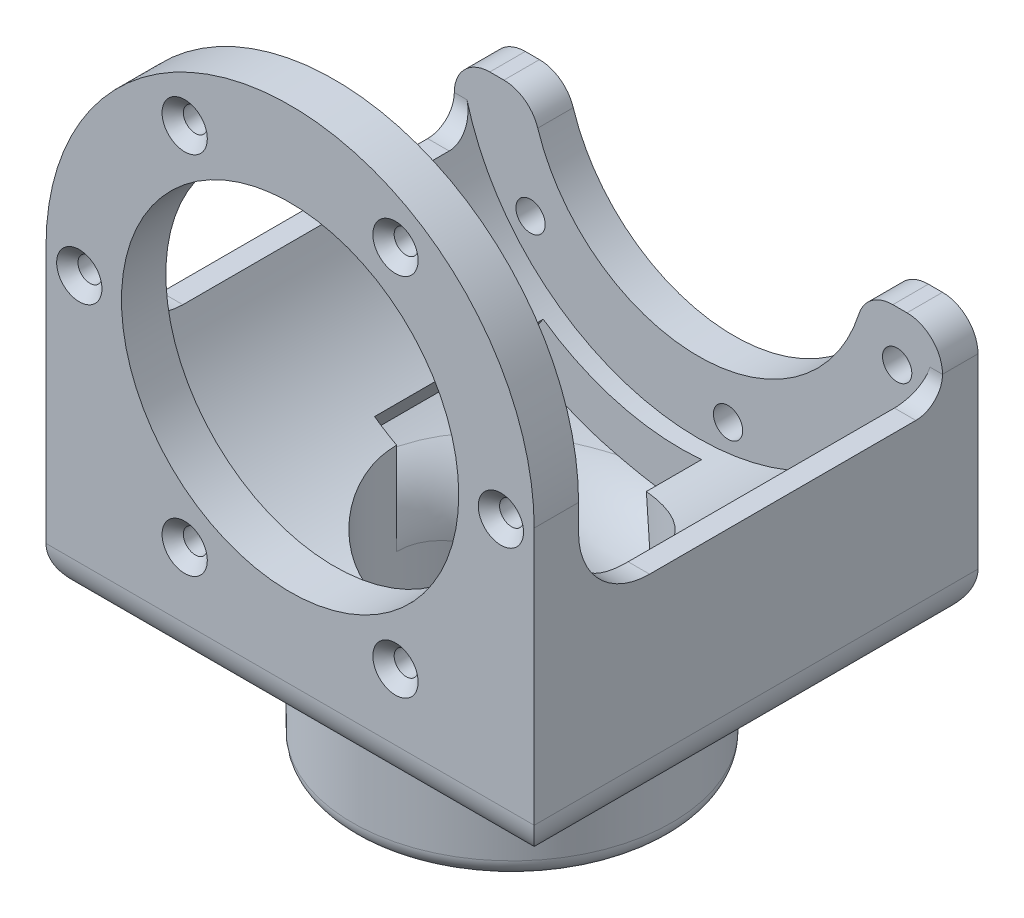
SolidWorks part; units mm, degrees
material "PLA"
ref_plane "Front Plane" through (0, 0, 0) normal (0, 0, 1) x (1, 0, 0)
ref_plane "Top Plane" through (0, 0, 0) normal (0, 1, 0) x (1, 0, 0)
ref_plane "Right Plane" through (0, 0, 0) normal (1, 0, 0) x (0, 0, -1)
sketch "Sketch1" plane through (0, 0, 0) normal (0, 1, 0) x (1, 0, 0)
  line L0 (0, 20.5) -> (0, -20.5) construction
  line L1 (-27.5, 20.5) -> (27.5, 20.5)
  line L2 (-27.5, 20.5) -> (-27.5, -20.5)
  line L3 (-27.5, -20.5) -> (27.5, -20.5)
  line L4 (27.5, 20.5) -> (27.5, -20.5)
  line L7 (27.5, 0) -> (0, 0) construction
  line L8 (0, 0) -> (-27.5, 0) construction
  dimension "D1" = 55
  dimension "D2" = 41
extrude "Boss-Extrude1" add sketch "Sketch1" along normal blind 23
sketch "Sketch3" plane through (0, 0, 20.5) normal (0, 0, 1) x (1, 0, 0)
  line L0 (27.5, 23) -> (27.5, 0) construction
  line L1 (-27.5, 0) -> (27.5, 0)
  line L2 (-27.5, 0) -> (-27.5, 33)
  line L3 (-27.5, 33) -> (27.5, 33) construction
  line L4 (27.5, 0) -> (27.5, 33)
  arc A0 (-27.5, 33) -> (27.5, 33) centre (0, 33) cw
  circle A1 centre (0, 33) radius 19
  circle A2 centre (0, 33) radius 18.5 construction
  dimension "D2" = 38
  dimension "D3" = 37
  dimension "D1" = 33
extrude "Boss-Extrude2" add sketch "Sketch3" along normal blind 5
sketch "Sketch5" plane through (0, 0, 25.5) normal (0, 0, 1) x (1, 0, 0)
  line L0 (-19, 33) -> (0, 33) construction
  line L1 (0, 33) -> (19, 33) construction
  line L2 (0, 33) -> (0, 14) construction
  line L3 (0, 33) -> (0, 52) construction
  line L4 (-19, 33) -> (-27.5, 33) construction
  line L5 (19, 33) -> (27.5, 33) construction
  line L6 (27.5, 34) -> (27.5, 33)
  line L7 (-27.5, 34) -> (-27.5, 33)
  circle A0 centre (0, 33) radius 19 construction
  arc A1 (-27.5, 33) -> (27.5, 33) centre (0, 33) cw
  arc A2 (27.5, 33) -> (-27.5, 33) centre (0, 33) ccw construction
  arc A3 (-27.5, 34) -> (27.5, 34) centre (0, 34) cw
  point P5 (0, 34)
  dimension "D2" = 27.5
  dimension "D1" = 1
extrude "Boss-Extrude3" add sketch "Sketch5" against normal up to surface (5 mm away) up to face at (0, 35.75, 20.5)
sketch "Sketch6" plane through (0, 0, 0) normal (0, -1, 0) x (1, 0, 0)
  line L0 (-27.5, 20.5) -> (27.5, 20.5) construction
  line L1 (-27.5, -20.5) -> (-27.5, 25.5) construction
  line L2 (27.5, 25.5) -> (27.5, -20.5) construction
  line L3 (-27.5, -19.5) -> (27.5, -19.5) construction
  line L5 (0, 20.5) -> (0, -19.5) construction
  line L6 (27.5, -20.5) -> (-27.5, -20.5) construction
  circle A0 centre (0, 0.5) radius 18
  dimension "D3" = 36
  dimension "D1" = 1
  dimension "D2" = 40
extrude "Boss-Extrude4" add sketch "Sketch6" along normal blind 14
sketch "Sketch4" plane through (0, 0, -20.5) normal (0, 0, -1) x (-1, 0, 0)
  line L0 (0, 0) -> (0, 6) construction
  line L1 (-19, 33) -> (0, 33) construction
  line L2 (0, 33) -> (19, 33) construction
  line L3 (0, 6) -> (0, 60) construction
  arc A1 (16.1555, 23) -> (-16.1555, 23) centre (0, 33) ccw construction
  circle A2 centre (0, 33) radius 26.5 construction
  circle A3 centre (0, 33) radius 18.5 construction
  circle A4 centre (0, 33) radius 27
  dimension "D1" = 53
  dimension "D2" = 37
  dimension "D3" = 54
extrude "Cut-Extrude1" cut sketch "Sketch4" against normal up to surface (41 mm away) up to face at (0, 36.0833, 20.5)
sketch "Sketch7" plane through (0, -14, 0) normal (0, -1, 0) x (1, 0, 0)
  circle A0 centre (0, 0.5) radius 13
  dimension "D1" = 26
extrude "Cut-Extrude2" cut sketch "Sketch7" against normal through all
sketch "Sketch8" plane through (0, 0, 25.5) normal (0, 0, 1) x (1, 0, 0)
  line L0 (0, 6) -> (0, 0) construction
  line L1 (-27.5, 0) -> (27.5, 0) construction
  line L2 (-5.45, 5.1) -> (5.45, 5.1)
  line L3 (-5.45, 5.1) -> (-5.45, 0.9)
  line L4 (-5.45, 0.9) -> (5.45, 0.9)
  line L5 (5.45, 5.1) -> (5.45, 0.9)
  circle A0 centre (0, 33) radius 27 construction
  point P10 (0, 0.9)
  dimension "D1" = 54
  dimension "D2" = 4.2
  dimension "D3" = 10.9
  dimension "D4" = 0.9
extrude "Cut-Extrude3" [suppressed] cut sketch "Sketch8" against normal up to surface (13.1976 mm away)
sketch "Sketch17" plane through (0, 0, -20.5) normal (0, 0, -1) x (-1, 0, 0)
  line L1 (-27.5, 23) -> (27.5, 23)
  line L2 (-27.5, 23) -> (-27.5, 0)
  line L3 (-27.5, 0) -> (27.5, 0)
  line L4 (27.5, 23) -> (27.5, 0)
extrude "Cut-Extrude5" cut sketch "Sketch17" against normal blind 1
ref_plane "Plane1" through (12.4779, 0, -12.4779) normal (0.7071, 0, -0.7071) x (0, 1, 0)
ref_axis "Axis1" through (0, 33, 25.5) along (0, 0, -1)
sketch "Sketch9" plane through (0, 0, 0) normal (1, 0, 0) x (0, 0, -1)
  line L0 (-0.5, -14) -> (-0.5, 23) construction
  line L1 (-18.5, -14) -> (17.5, -14) construction
  line L2 (-20.5, 23) -> (19.5, 23) construction
  line L3 (-25.5, 0) -> (19.5, 0) construction
  line L4 (-0.5, 8) -> (18.5, 8)
  line L5 (-0.5, 8) -> (-0.5, 1)
  line L6 (-0.5, 1) -> (18.5, 1)
  line L7 (18.5, 8) -> (18.5, 1)
  dimension "D1" = 19
  dimension "D2" = 7
  dimension "D3" = 1
revolve "Cut-Revolve1" cut sketch "Sketch9" angle 35 about axis through (0, 33, 25.5) along (0, 0, -1) other way angle 5
hole_wizard "CSK for M2.5 Flat Head Machine Screw2" positions "Sketch14" profile "Sketch13" countersink size "M2.5" standard "ANSI Metric" end condition through all
sketch "Sketch14" plane through (0, 0, 25.5) normal (0, 0, 1) x (1, 0, 0)
  line L0 (0, 33) -> (-23.75, 33) construction
  point P2 (-23.75, 33)
  dimension "D1" = 23.75
sketch "Sketch13" plane through (-23.75, 33, 25.5) normal (1, 0, 0) x (0, -1, 0)
  line L0 (0, 0) -> (0, 45)
  line L1 (0, 45) -> (1.35, 45)
  line L2 (1.35, 45) -> (1.35, 1.2)
  line L3 (1.35, 1.2) -> (2.55, 0)
  line L5 (2.55, 0) -> (0, 0)
  line L6 (-1.35, 1.2) -> (-2.55, 0) construction
  line L11 (0, -6.35) -> (0, 107.95) construction
  dimension "Thru Hole Dia." = 2.7
  dimension "Thru Hole Depth" = 45
  dimension "Near C'Sink Dia." = 5.1
  dimension "Near C'Sink Angle" = 90
pattern_circular "CirPattern1" count 6 over 360 about axis through (0, 33, 25.5) along (0, 0, -1) of "CSK for M2.5 Flat Head Machine Screw2"
sketch "Sketch16" plane through (12.4779, 0, -12.4779) normal (0.7071, 0, -0.7071) x (0, 1, 0)
  line L0 (-14, 18.3536) -> (-14, -17.6464) construction
  line L4 (-14, 0.3536) -> (0, 0.3536) construction
  line L5 (0, 5.6569) -> (0, -33.234) construction
  line L6 (0, 18.3536) -> (0, -17.6464) construction
  circle A1 centre (-5.2, 0.3536) radius 1.4
  dimension "D1" = 2.8
  dimension "D2" = 5.2
extrude "Cut-Extrude4" cut sketch "Sketch16" against normal blind 4
pattern_circular "CirPattern2" count 4 over 360 about axis through (0, 61.5, 0.5) along (0, -1, 0) of "Cut-Extrude4" reverse direction yes
sketch "Sketch19" plane through (0, 0, -19.5) normal (0, 0, -1) x (-1, 0, 0)
  line L0 (0, 33) -> (0, 9) construction
  line L1 (0, 33) -> (-3.3816, 9.2394) construction
  line L2 (-27.5, 0) -> (27.5, 0)
  line L3 (27.5, 0) -> (27.5, 30)
  line L4 (0, 33) -> (-22.2681, 24.0483) construction
  line L5 (27.5, 30) -> (18.7617, 30)
  line L6 (0, 33) -> (18.8864, 18.1911) construction
  line L7 (-27.5, 30) -> (-27.5, 0)
  line L8 (-18.7617, 30) -> (-27.5, 30)
  circle A0 centre (0, 33) radius 24 construction
  circle A1 centre (-3.3816, 9.2394) radius 1.55 construction
  circle A2 centre (-22.2681, 24.0483) radius 1.55 construction
  circle A5 centre (18.8864, 18.1911) radius 1.55 construction
  arc A6 (-18.7617, 30) -> (18.7617, 30) centre (0, 33) ccw
  circle A7 centre (0, 33) radius 19 construction
  point P12 (0, 33)
  point P13 (0, 33)
  dimension "D1" = 48
  dimension "D2" = 8.1
  dimension "D3" = 3.1
  dimension "D6" = 30
extrude "Boss-Extrude5" add sketch "Sketch19" along normal blind 5
sketch "Sketch25" plane through (0, 0, -24.5) normal (0, 0, -1) x (-1, 0, 0)
  line L0 (0, 14) -> (0, 33) construction
  line L1 (-3.3402, 9.2336) -> (0, 33) construction
  line L2 (0, 33) -> (-22.3909, 24.3601) construction
  line L3 (0, 33) -> (18.9123, 18.2241) construction
  circle A0 centre (0, 33) radius 24 construction
  arc A4 (-18.7617, 30) -> (18.7617, 30) centre (0, 33) ccw construction
  circle A5 centre (-3.3402, 9.2336) radius 1.4447 construction
  circle A6 centre (18.9123, 18.2241) radius 1.094 construction
  circle A7 centre (-22.3909, 24.3601) radius 1.7903 construction
  dimension "D1" = 48
  dimension "D4" = 60.9
  dimension "D2" = 8
  dimension "D3" = 60
sketch "Sketch22" plane through (0, 30, 0) normal (0, 1, 0) x (1, 0, 0)
  line L0 (27.5, 24.5) -> (27.5, 19.5) construction
  line L1 (-27.5, 19.5) -> (27.5, 19.5)
  line L2 (-27.5, 19.5) -> (-27.5, 20.5)
  line L3 (-27.5, 20.5) -> (27.5, 20.5)
  line L4 (27.5, 19.5) -> (27.5, 20.5)
  dimension "D1" = 1
extrude "Cut-Extrude6" cut sketch "Sketch22" against normal up to surface (7 mm away) up to face at (-5.472, 8.1822, -6.1909)
extrude "Cut-Extrude7" cut sketch "Sketch22<2>" against normal up to surface (7 mm away) up to face at (26.2899, 23, 0.5)
sketch "Sketch22<2>" plane through (0, 30, 0) normal (0, 1, 0) x (1, 0, 0) same geometry as "Sketch22"
hole_wizard "CSK for M3 Flat Head Machine Screw1" positions "Sketch20" profile "Sketch21" countersink size "M3" standard "ANSI Metric"
sketch "Sketch20" plane through (0, 0, -24.5) normal (0, 0, -1) x (-1, 0, 0)
  point P60 (-22.3909, 24.3601)
  point P63 (-3.3402, 9.2336)
  point P71 (18.9123, 18.2241)
sketch "Sketch21" plane through (22.3909, 24.3601, -24.5) normal (1, 0, 0) x (0, 1, 0)
  line L0 (0, 0) -> (0, 12)
  line L1 (0, 12) -> (1.65, 12)
  line L2 (1.65, 12) -> (1.65, 1.5)
  line L3 (1.65, 1.5) -> (3.15, 0)
  line L5 (3.15, 0) -> (0, 0)
  line L6 (-1.65, 1.5) -> (-3.15, 0) construction
  line L10 (0, 12) -> (-1.65, 12) construction
  line L11 (0, -6.35) -> (0, 107.95) construction
  dimension "Hole Dia." = 3.3
  dimension "Hole Depth" = 12
  dimension "Near C'Sink Dia." = 6.3
  dimension "Near C'Sink Angle" = 90
  dimension "Drill Angle" = 180
fillet "Fillet1" radius 2 1 edges at (0, -14, -17.5)
fillet "Fillet2" radius 8 1 edges at (-8.6521, 2.1919, -9.2026)
fillet "Fillet3" radius 5 4 edges at (27.5, 0, 0.5) (0, 0, 25.5) (-27.5, 0, 0.5) (0, 0, -24.5)
fillet "Fillet6" radius 8 2 edges at (-26.2899, 23, 20.5) (26.2899, 23, 20.5)
fillet "Fillet7" radius 4 4 edges at (-27.5, 30, -22.5) (-18.7617, 30, -22.5) (18.7617, 30, -22.5) (27.5, 30, -22.5)
fillet "Fillet8" radius 3 2 edges at (-26.2899, 23, -20.5) (26.2899, 23, -20.5)
sketch "Sketch27" plane through (0, 0, 25.5) normal (0, 0, 1) x (1, 0, 0)
  line L1 (-33.265, 65.2394) -> (37.3857, 65.2394)
  line L2 (-33.265, 65.2394) -> (-33.265, -15.0296)
  line L3 (-33.265, -15.0296) -> (37.3857, -15.0296)
  line L4 (37.3857, 65.2394) -> (37.3857, -15.0296)
extrude "Cut-Extrude8" [suppressed] cut sketch "Sketch27" against normal up to vertex
sketch "Sketch28" plane through (0, 23, 0) normal (0, 1, 0) x (1, 0, 0)
  line L0 (-18.0987, 20.5) -> (18.0987, 20.5) construction
  line L1 (-0.9257, 20.5) -> (46.0253, 20.5)
  line L2 (-41.1901, 20.5) -> (-41.1901, -57.2501)
  line L3 (-41.1901, -57.2501) -> (46.0253, -57.2501)
  line L4 (46.0253, 20.5) -> (46.0253, -57.2501)
  line L7 (-41.1901, 20.5) -> (-41.1901, 37.8555)
  line L8 (-41.1901, 37.8555) -> (-0.9257, 37.8555)
  line L9 (-0.9257, 20.5) -> (-0.9257, 37.8555)
extrude "Cut-Test" [suppressed] cut sketch "Sketch28" along normal through all
sketch "Sketch29" plane through (0, 0, 0) normal (0, -1, 0) x (1, 0, 0)
  line L1 (-33.2461, 33.9996) -> (38.7573, 33.9996)
  line L2 (-33.2461, 33.9996) -> (-33.2461, -37.6657)
  line L3 (-33.2461, -37.6657) -> (38.7573, -37.6657)
  line L4 (38.7573, 33.9996) -> (38.7573, -37.6657)
extrude "Cut-Extrude10" [suppressed] cut sketch "Sketch29" against normal blind 5.2 and the other way through all
sketch "Sketch30" plane through (0, 23, 0) normal (0, 1, 0) x (1, 0, 0)
  line L0 (25.0799, 20.5) -> (25.0799, -20.5) construction
  line L1 (26.5799, 20.5) -> (23.5799, 20.5)
  line L2 (26.5799, 20.5) -> (26.5799, -20.5)
  line L3 (26.5799, -20.5) -> (23.5799, -20.5)
  line L4 (23.5799, 20.5) -> (23.5799, -20.5)
  line L5 (25.0799, -20.5) -> (25.0799, 20.5) construction
  dimension "D1" = 1.5
  dimension "D2" = 1.5
extrude "Cut-Extrude11" [suppressed] cut sketch "Sketch30" against normal through all
sketch "Sketch31" plane through (27.5, 0, 0) normal (1, 0, 0) x (0, 0, -1)
  line L0 (-12.5, 23) -> (17.5, 23) construction
  line L1 (-17.5, 23) -> (17.5, 23)
  line L2 (-17.5, 23) -> (-17.5, 11)
  line L3 (-17.5, 11) -> (17.5, 11)
  line L4 (17.5, 23) -> (17.5, 11)
  line L5 (-25.5, 5) -> (-25.5, 34) construction
  dimension "D1" = 35
  dimension "D2" = 8
  dimension "D3" = 12
extrude "Cut-Extrude12" [suppressed] cut sketch "Sketch31" against normal through all
sketch "Sketch32" plane through (0, 23, 0) normal (0, 1, 0) x (1, 0, 0)
  line L1 (-41.0286, -5.8554) -> (34.2896, -5.8554)
  line L2 (-41.0286, -5.8554) -> (-41.0286, -27.6883)
  line L3 (-41.0286, -27.6883) -> (34.2896, -27.6883)
  line L4 (34.2896, -5.8554) -> (34.2896, -27.6883)
extrude "Cut-Extrude13" [suppressed] cut sketch "Sketch32" against normal blind 7
fillet "Fillet9" [suppressed] radius 3 type face fillet
sketch "Sketch33" plane through (0, 0, -24.5) normal (0, 0, -1) x (-1, 0, 0)
  line L0 (-19.5, 7.5) -> (27.5, 7.5) construction
  line L1 (-27.5, 26) -> (-27.5, 5) construction
  line L2 (27.5, 5) -> (27.5, 26) construction
  line L3 (-27.5, 5) -> (27.5, 5) construction
  line L4 (-19.5, 5) -> (-19.5, 7.5) construction
  text T0 "<b>3</b>" font "Century Gothic" height 3.5
  dimension "D1" = 2.5
  dimension "D2" = 8
extrude "Cut-Extrude14" cut sketch "Sketch33" against normal blind 1
